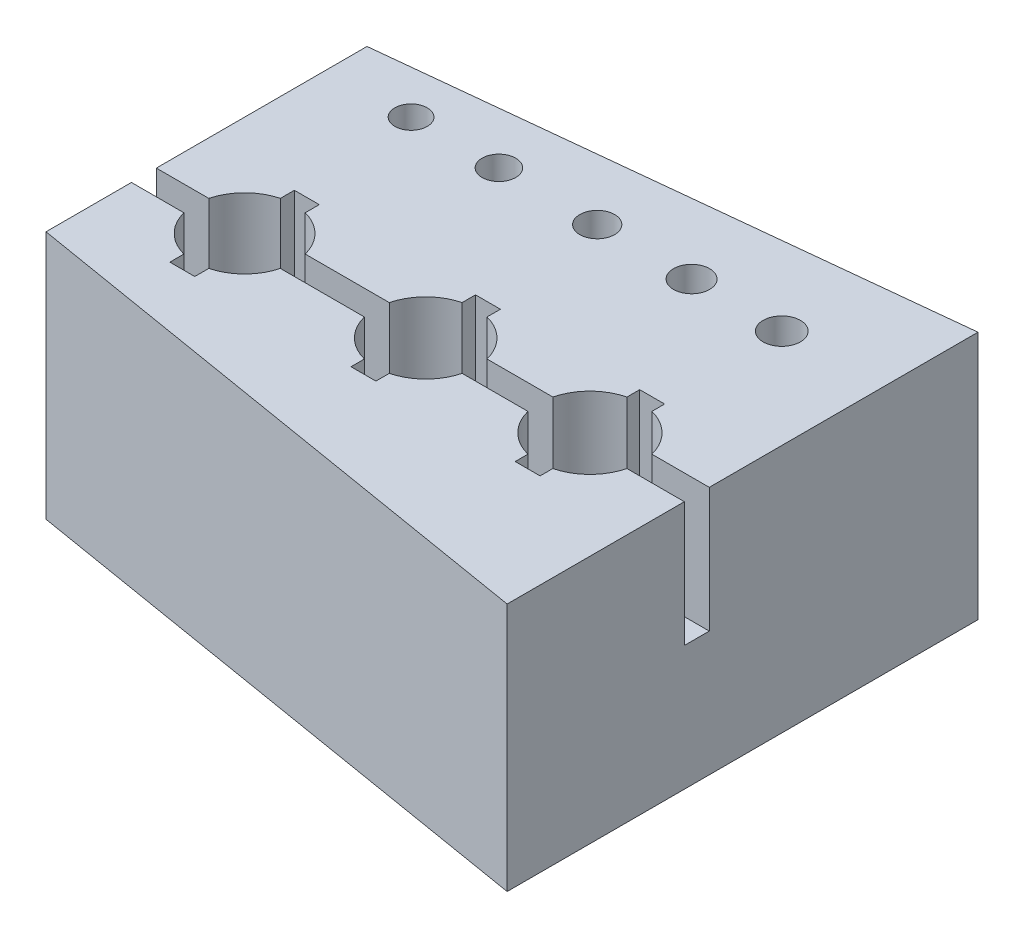
SolidWorks part; units mm, degrees
ref_plane "Front Plane" through (0, 0, 0) normal (0, 0, 1) x (1, 0, 0)
ref_plane "Top Plane" through (0, 0, 0) normal (0, 1, 0) x (1, 0, 0)
ref_plane "Right Plane" through (0, 0, 0) normal (1, 0, 0) x (0, 0, -1)
sketch "Sketch1" plane through (0, 0, 0) normal (0, 1, 0) x (1, 0, 0)
  line L0 (0, 1.9938) -> (22.2066, -1.6931) construction
  line L1 (22.2066, -1.6931) -> (22.2066, 6.1153)
  line L2 (22.2066, 6.1153) -> (0, 3.7836)
  line L3 (0, 3.7836) -> (0, 1.9938)
  line L4 (0, 1.9938) -> (0, -9.1076)
  line L5 (0, -9.1076) -> (22.2066, -12.7945)
  line L6 (22.2066, -12.7945) -> (22.2066, -1.6931)
  line L7 (0, -5.1766) -> (22.2066, -5.1766) construction
  line L8 (0, 2.2111) -> (22.2066, 2.2111) construction
  line L10 (0, -4.6766) -> (22.2066, -4.6766)
  line L11 (0, -4.6766) -> (0, -5.6766)
  line L12 (0, -5.6766) -> (22.2066, -5.6766)
  line L13 (22.2066, -4.6766) -> (22.2066, -5.6766)
  line L14 (3.5433, -2.6766) -> (4.5433, -2.6766)
  line L15 (3.5433, -2.6766) -> (3.5433, -7.6766)
  line L16 (3.5433, -7.6766) -> (4.5433, -7.6766)
  line L17 (4.5433, -2.6766) -> (4.5433, -7.6766)
  line L22 (10.8179, -2.6766) -> (11.8179, -2.6766)
  line L23 (10.8179, -2.6766) -> (10.8179, -7.6766)
  line L24 (10.8179, -7.6766) -> (11.8179, -7.6766)
  line L25 (11.8179, -2.6766) -> (11.8179, -7.6766)
  line L26 (10.8179, -2.6766) -> (11.8179, -7.6766) construction
  line L27 (10.8179, -7.6766) -> (11.8179, -2.6766) construction
  line L28 (17.4121, -2.6766) -> (18.4121, -2.6766)
  line L29 (17.4121, -2.6766) -> (17.4121, -7.6766)
  line L30 (17.4121, -7.6766) -> (18.4121, -7.6766)
  line L31 (18.4121, -2.6766) -> (18.4121, -7.6766)
  line L32 (17.4121, -2.6766) -> (18.4121, -7.6766) construction
  line L33 (17.4121, -7.6766) -> (18.4121, -2.6766) construction
  circle A0 centre (3.3423, 2.2111) radius 0.65
  circle A1 centre (6.8702, 2.2111) radius 0.675
  circle A2 centre (10.8179, 2.2111) radius 0.7
  circle A3 centre (14.6074, 2.2111) radius 0.725
  circle A4 centre (18.23, 2.2111) radius 0.75
  circle A5 centre (4.0433, -5.1766) radius 2
  circle A6 centre (11.3179, -5.1766) radius 2.025
  circle A7 centre (17.9121, -5.1766) radius 2.05
  point P7 (22.2066, 2.2111)
  point P27 (4.0433, -7.6766)
  point P30 (3.5433, -5.1766)
  point P46 (22.0839, -11.7744)
  point P47 (0, 3.7836)
  point P48 (22.2066, 4.6152)
  point P49 (17.6345, 2.2483)
  point P50 (14.1881, 2.185)
  point P51 (10.504, 2.2632)
  point P52 (7.2702, 2.2024)
  point P53 (3.3423, 2.2536)
  point P54 (6.8702, 2.1724)
  point P55 (10.8179, 2.1467)
  point P56 (18.23, 2.1439)
  point P57 (14.6074, 2.2111)
  dimension "D1" = 1.3
  dimension "D2" = 1.35
  dimension "D3" = 1.4
  dimension "D4" = 1.45
  dimension "D5" = 1.5
  dimension "D6" = 4
  dimension "D7" = 4.05
  dimension "D8" = 4.1
  dimension "D9" = 1
  dimension "D10" = 5
  dimension "D11" = 1
  dimension "D12" = 0.5
  dimension "D13" = 5
  dimension "D14" = 1
  dimension "D15" = 1
  dimension "D16" = 5
extrude "Boss-Extrude1" add sketch "Sketch1" along normal blind 10 contours A7 L10 L6 L1 L2 L3 L4 A5 L15 L14 L17 A6 L23 L22 L25 L29 L28 L31 A4 A3 A2 A1 A0 | A7 L31 L30 L29 L12 A6 L25 L24 L23 A5 L17 L16 L15 L4 L5 L6 | A7 L12 L6 L10 | L12 A7 L10 L31 | L10 A7 L31 | A7 L31 L28 L29 | L31 A7 L29 L10 | L31 A7 L12 | L29 A7 L31 L12 | A7 L29 L30 L31 | L31 L10 L29 L12 | L10 A7 L12 L29 | L29 A7 L10 | L12 A7 L29 | A7 L10 A6 L12 | L10 A6 L25 | A6 L25 L22 L23 | L25 A6 L23 L10 | L12 A6 L10 L25 | L25 A6 L12 | L23 A6 L25 L12 | A6 L23 L24 L25 | L25 L10 L23 L12 | L10 A6 L12 L23 | L23 A6 L10 | L12 A6 L23 | A6 L10 A5 L12 | L10 A5 L17 | L12 A5 L10 L17 | L17 A5 L12 | L15 A5 L17 L12 | A5 L15 L16 L17 | L12 A5 L15 | L10 A5 L12 L15 | L17 L10 L15 L12 | L17 A5 L15 L10 | A5 L17 L14 L15 | L15 A5 L10 | A5 L10 L4 L12 region at (11.5891, 0, -0.3936) region at (21.074, 0, 5.1766) region at (12.571, 0, 8.71) region at (19.177, 0, 5.1766) region at (18.9982, 0, 4.0905) region at (18.9982, 0, 6.2626) region at (17.9121, 0, 5.1766) region at (17.9121, 0, 3.9117) region at (17.9121, 0, 2.9122) region at (1.0323, 0, 5.1766) region at (17.9121, 0, 6.4414) region at (17.9121, 0, 7.441) region at (16.6473, 0, 5.1766) region at (16.8261, 0, 4.0905) region at (2.9787, 0, 4.1119) region at (2.8037, 0, 5.1766) region at (16.8261, 0, 6.2626) region at (14.6024, 0, 5.1766) region at (2.9787, 0, 6.2412) region at (4.0433, 0, 3.937) region at (4.0433, 0, 5.1766) region at (4.0433, 0, 2.9374) region at (12.5701, 0, 5.1766) region at (12.3933, 0, 4.1012) region at (4.0433, 0, 6.4162) region at (4.0433, 0, 7.4157) region at (5.108, 0, 4.1119) region at (5.2829, 0, 5.1766) region at (12.3933, 0, 6.2519) region at (11.3179, 0, 5.1766) region at (11.3179, 0, 3.9243) region at (11.3179, 0, 2.9248) region at (5.108, 0, 6.2412) region at (7.668, 0, 5.1766) region at (11.3179, 0, 6.4288) region at (11.3179, 0, 7.4283) region at (10.0657, 0, 5.1766) region at (10.2426, 0, 4.1012) region at (10.2426, 0, 6.2519)
extrude "Cut-Extrude1" cut sketch "Sketch1<4>" against normal blind 5 from surface contours A7 L12 L6 L10 | L12 A7 L10 L31 | L10 A7 L31 | L31 A7 L12 | A7 L29 L30 L31 | L29 A7 L31 L12 | L31 L10 L29 L12 | L31 A7 L29 L10 | A7 L31 L28 L29 | L29 A7 L10 | L10 A7 L12 L29 | L12 A7 L29 | A7 L10 A6 L12 | L12 A6 L10 L25 | L25 A6 L12 | A6 L23 L24 L25 | L23 A6 L25 L12 | L25 L10 L23 L12 | L25 A6 L23 L10 | L10 A6 L25 | A6 L25 L22 L23 | L23 A6 L10 | L10 A6 L12 L23 | L12 A6 L23 | A6 L10 A5 L12 | L12 A5 L10 L17 | L10 A5 L17 | A5 L17 L14 L15 | L17 A5 L15 L10 | L15 A5 L17 L12 | L17 L10 L15 L12 | L17 A5 L12 | A5 L15 L16 L17 | L12 A5 L15 | L10 A5 L12 L15 | L15 A5 L10 | A5 L10 L4 L12 region at (21.074, 0, 5.1766) region at (19.177, 0, 5.1766) region at (18.9982, 0, 4.0905) region at (18.9982, 0, 6.2626) region at (17.9121, 0, 5.1766) region at (17.9121, 0, 3.9117) region at (17.9121, 0, 2.9122) region at (1.0323, 0, 5.1766) region at (17.9121, 0, 6.4414) region at (17.9121, 0, 7.441) region at (16.6473, 0, 5.1766) region at (16.8261, 0, 4.0905) region at (2.9787, 0, 4.1119) region at (2.8037, 0, 5.1766) region at (16.8261, 0, 6.2626) region at (14.6024, 0, 5.1766) region at (2.9787, 0, 6.2412) region at (4.0433, 0, 3.937) region at (4.0433, 0, 5.1766) region at (4.0433, 0, 2.9374) region at (12.5701, 0, 5.1766) region at (12.3933, 0, 4.1012) region at (4.0433, 0, 6.4162) region at (4.0433, 0, 7.4157) region at (5.108, 0, 4.1119) region at (5.2829, 0, 5.1766) region at (12.3933, 0, 6.2519) region at (11.3179, 0, 5.1766) region at (11.3179, 0, 3.9243) region at (11.3179, 0, 2.9248) region at (5.108, 0, 6.2412) region at (7.668, 0, 5.1766) region at (11.3179, 0, 6.4288) region at (11.3179, 0, 7.4283) region at (10.0657, 0, 5.1766) region at (10.2426, 0, 4.1012) region at (10.2426, 0, 6.2519) starting at face at (11.1033, 10, 3.0008)
sketch "Sketch1<4>" plane through (0, 0, 0) normal (0, 1, 0) x (1, 0, 0) same geometry as "Sketch1"
